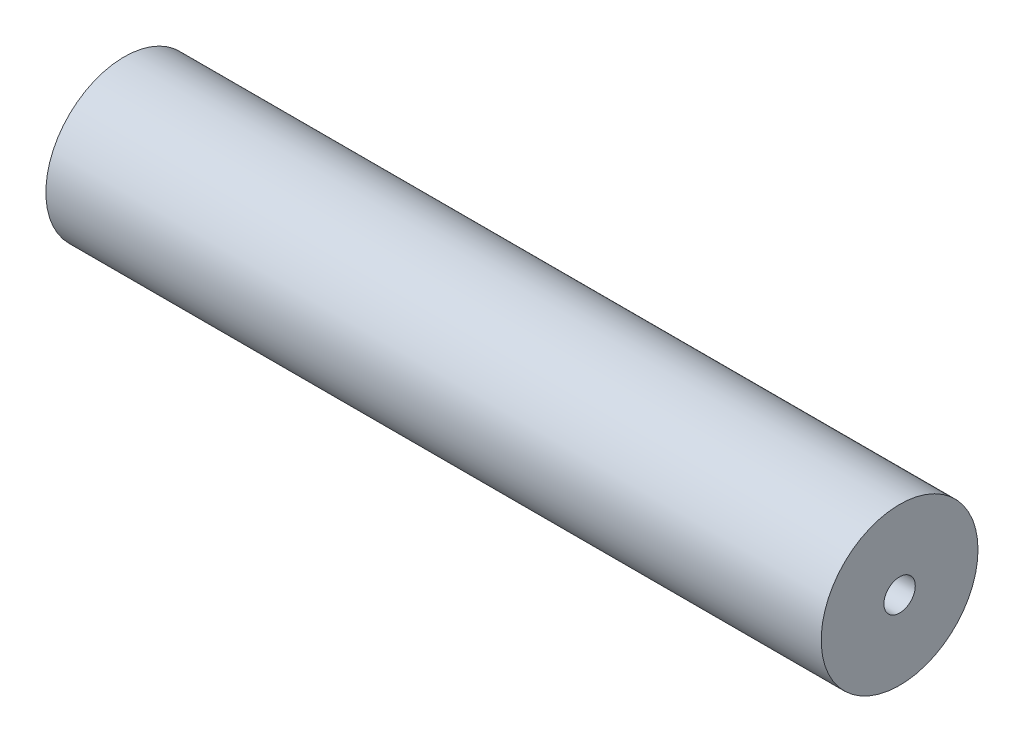
SolidWorks part; units mm, degrees
material "Oak"
ref_plane "Front" through (0, 0, 0) normal (0, 0, 1) x (1, 0, 0)
ref_plane "Top" through (0, 0, 0) normal (0, 1, 0) x (1, 0, 0)
ref_plane "Right" through (0, 0, 0) normal (1, 0, 0) x (0, 0, -1)
ref_axis "side-side" through (80.9, 0, 0) along (-1, 0, 0)
ref_axis "up-down" through (0, 50, 0) along (0, -1, 0)
ref_axis "front-back" through (0, 0, -80.9) along (0, 0, 1)
sketch "Sketch1" plane through (0, 0, 0) normal (0, 0, 1) x (1, 0, 0)
  line L0 (0, 0) -> (-61.4641, 0) construction
  line L2 (0, 7.9375) -> (78.5, 7.9375)
  line L3 (0, 7.9375) -> (0, 1.5875)
  line L4 (10, 0) -> (68.5, 0)
  line L5 (78.5, 7.9375) -> (78.5, 1.5875)
  line L8 (0, 1.5875) -> (10, 1.5875)
  line L9 (10, 0) -> (10, 1.5875)
  line L10 (78.5, 1.5875) -> (68.5, 1.5875)
  line L13 (68.5, 1.5875) -> (68.5, 0)
  dimension "D1" = 3.175
  dimension "D2" = 10
  dimension "D3" = 15.875
  dimension "D4" = 78.5
revolve "Revolve1" add sketch "Sketch1" angle 360 about L0
